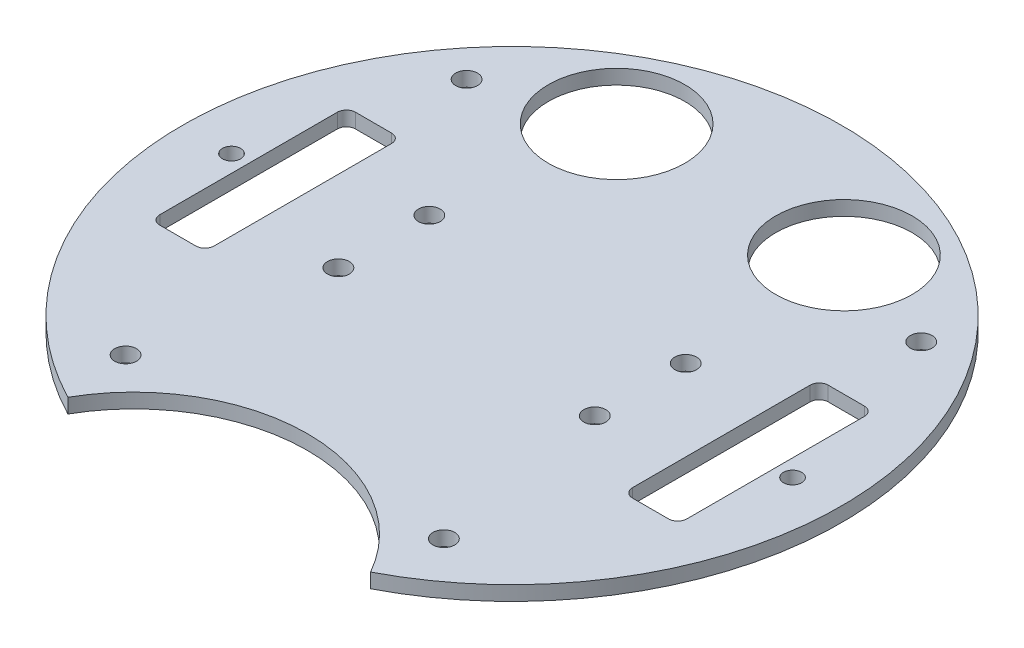
SolidWorks part; units mm, degrees
material "Plain Carbon Steel"
ref_plane "Front Plane" through (0, 0, 0) normal (0, 0, 1) x (1, 0, 0)
ref_plane "Top Plane" through (0, 0, 0) normal (0, 1, 0) x (1, 0, 0)
ref_plane "Right Plane" through (0, 0, 0) normal (1, 0, 0) x (0, 0, -1)
sketch "Sketch1" plane through (0, 0, 0) normal (0, 1, 0) x (1, 0, 0)
  line L0 (0, -83.2398) -> (-33.2911, -64.4046) construction
  line L1 (0, -83.2398) -> (0, 0) construction
  arc A0 (33.2911, -64.4046) -> (-33.2911, -64.4046) centre (0, 0) ccw
  arc A1 (33.2911, -64.4046) -> (-33.2911, -64.4046) centre (0, -83.2398) ccw
  dimension "D1" = 145
  dimension "D2" = 76.5
  dimension "D3" = 60.5
extrude "Boss-Extrude1" add sketch "Sketch1" along normal blind 3.2
sketch "solenoid placement" plane through (0, 3.2, 0) normal (0, 1, 0) x (1, 0, 0)
  line L0 (0, 0) -> (0, -36) construction
  line L1 (0, -36) -> (0, -44.9898) construction
  line L2 (-19, -36) -> (19, -36)
  line L3 (-19, -36) -> (-19, 28.4)
  line L4 (-19, 28.4) -> (19, 28.4)
  line L5 (19, -36) -> (19, 28.4)
  circle A1 centre (0, 0) radius 72.5 construction
  arc A2 (33.2911, -64.4046) -> (-33.2911, -64.4046) centre (0, 0) ccw construction
  arc A3 (33.2911, -64.4046) -> (-33.2911, -64.4046) centre (0, -83.2398) ccw construction
  dimension "D1" = 64.4
  dimension "D2" = 36
  dimension "D4" = 38
sketch "Sketch2" plane through (0, 3.2, 0) normal (0, 1, 0) x (1, 0, 0)
  line L1 (-57.07, 20.6344) -> (-46.91, 20.6344) construction
  line L2 (-57.07, 20.6344) -> (-57.07, -20.6344) construction
  line L3 (-57.07, -20.6344) -> (-46.91, -20.6344) construction
  line L4 (-46.91, 20.6344) -> (-46.91, -20.6344) construction
  line L8 (-57.37, -20.9344) -> (-46.61, -20.9344)
  line L9 (-46.61, 20.9344) -> (-46.61, -20.9344)
  line L10 (-57.37, 20.9344) -> (-46.61, 20.9344)
  line L11 (-57.37, 20.9344) -> (-57.37, -20.9344)
  line L12 (0, 0) -> (0, 72.5) construction
  line L13 (46.91, 20.6344) -> (46.91, -20.6344) construction
  line L14 (57.07, -20.6344) -> (46.91, -20.6344) construction
  line L15 (57.07, 20.6344) -> (57.07, -20.6344) construction
  line L16 (57.07, 20.6344) -> (46.91, 20.6344) construction
  line L17 (57.37, 20.9344) -> (57.37, -20.9344)
  line L18 (57.37, 20.9344) -> (46.61, 20.9344)
  line L19 (46.61, 20.9344) -> (46.61, -20.9344)
  line L20 (57.37, -20.9344) -> (46.61, -20.9344)
  arc A0 (33.2911, -64.4046) -> (-33.2911, -64.4046) centre (0, 0) ccw construction
extrude "Cut-Extrude1" cut sketch "Sketch2" against normal through all
sketch "Sketch3" plane through (0, 0, 0) normal (0, -1, 0) x (1, 0, 0)
  line L0 (0, 0) -> (0, -72.5) construction
  circle A0 centre (-61.7, 0) radius 2
  circle A1 centre (-28.2, 10) radius 2.4
  circle A2 centre (-28.2, -10) radius 2.4
  arc A3 (-33.2911, 64.4046) -> (33.2911, 64.4046) centre (0, 0) ccw construction
  circle A4 centre (28.2, -10) radius 2.4
  circle A5 centre (28.2, 10) radius 2.4
  circle A6 centre (61.7, 0) radius 2
  dimension "D1" = 4
  dimension "D2" = 4.8
extrude "Cut-Extrude2" cut sketch "Sketch3" against normal through all
sketch "Sketch4" plane through (0, 3.2, 0) normal (0, 1, 0) x (1, 0, 0)
  line L0 (0, 0) -> (0, 72.5) construction
  line L1 (0, 48) -> (-25, 48) construction
  circle A0 centre (-25, 48) radius 15
  arc A1 (33.2911, -64.4046) -> (-33.2911, -64.4046) centre (0, 0) ccw construction
  circle A2 centre (25, 48) radius 15
  dimension "D1" = 30
  dimension "D2" = 48
  dimension "D3" = 25
extrude "Cut-Extrude3" cut sketch "Sketch4" against normal through all
sketch "Sketch5" plane through (0, 3.2, 0) normal (0, 1, 0) x (1, 0, 0)
  line L0 (0, 0) -> (0, 72.5) construction
  line L1 (-55.9558, 21.5201) -> (-48.0242, 21.5201)
  line L2 (-57.9558, 19.5201) -> (-57.9558, -19.5201)
  line L3 (-55.9558, -21.5201) -> (-48.0242, -21.5201)
  line L4 (-46.0242, 19.5201) -> (-46.0242, -19.5201)
  line L5 (46.0242, 19.5201) -> (46.0242, -19.5201)
  line L6 (55.9558, -21.5201) -> (48.0242, -21.5201)
  line L7 (57.9558, 19.5201) -> (57.9558, -19.5201)
  line L8 (55.9558, 21.5201) -> (48.0242, 21.5201)
  arc A0 (-57.9558, -19.5201) -> (-55.9558, -21.5201) centre (-55.9558, -19.5201) ccw
  arc A1 (-48.0242, -21.5201) -> (-46.0242, -19.5201) centre (-48.0242, -19.5201) ccw
  arc A2 (-48.0242, 21.5201) -> (-46.0242, 19.5201) centre (-48.0242, 19.5201) cw
  arc A3 (-55.9558, 21.5201) -> (-57.9558, 19.5201) centre (-55.9558, 19.5201) ccw
  arc A4 (33.2911, -64.4046) -> (-33.2911, -64.4046) centre (0, 0) ccw construction
  arc A5 (55.9558, 21.5201) -> (57.9558, 19.5201) centre (55.9558, 19.5201) cw
  arc A6 (48.0242, 21.5201) -> (46.0242, 19.5201) centre (48.0242, 19.5201) ccw
  arc A7 (48.0242, -21.5201) -> (46.0242, -19.5201) centre (48.0242, -19.5201) cw
  arc A8 (57.9558, -19.5201) -> (55.9558, -21.5201) centre (55.9558, -19.5201) cw
  point P15 (-57.37, 20.9344)
  dimension "D1" = 2
extrude "Cut-Extrude4" cut sketch "Sketch5" against normal through all
sketch "Sketch6" plane through (0, 3.2, 0) normal (0, 1, 0) x (1, 0, 0)
  line L0 (0, 72.5) -> (0, -44.9898) construction
  circle A0 centre (-50, 40) radius 2.4
  circle A1 centre (-35, -50) radius 2.4
  arc A4 (33.2911, -64.4046) -> (-33.2911, -64.4046) centre (0, 0) ccw construction
  arc A5 (33.2911, -64.4046) -> (-33.2911, -64.4046) centre (0, -83.2398) ccw construction
  circle A6 centre (35, -50) radius 2.4
  circle A7 centre (50, 40) radius 2.4
  dimension "D3" = 4.8
  dimension "D1" = 35
  dimension "D2" = 50
  dimension "D4" = 50
  dimension "D5" = 40
extrude "Cut-Extrude5" cut sketch "Sketch6" against normal through all
chamfer "Chamfer1" [suppressed] distance 2 angle 41
equation "\"smallPulleyTeeth\"= 15"
equation "\"largePulleyTeeth\"= 30"
equation "\"eighthThick\"= 2.9mm"
equation "\"sixteenthThick\" = 1.7mm"
equation "\"quarterThick\"=6.0mm"
equation "\"OD\" = 145mm"
equation "\"puckAngle\" = 60.5deg"
equation "\"D1@Sketch1\"=\"OD\""
equation "\"puckDiam\" = 76.5mm"
equation "\"D2@Sketch1\"=\"puckDiam\""
equation "\"D3@Sketch1\"=\"puckAngle\""
equation "\"D1@Boss-Extrude1\"=\"eighthThick\""
equation "\"axlePress\" = 5.9mm"
equation "\"press\" = 0.2mm"
equation "\"wheelClear\" = 0.3mm"
equation "\"D1@Sketch2\"=\"wheelClear\""
equation "\"10-32clear\" = 4.8mm"
equation "\"6-32clear\" = 3.3mm"
equation "\"8-32clear\" = 4.0mm"
equation "\"wheelHeight\" = 22mm"
equation "\"D1@Sketch3\"=\"8-32clear\""
equation "\"D2@Sketch3\"=\"10-32clear\""
equation "\"D3@Sketch6\"=\"10-32clear\""
